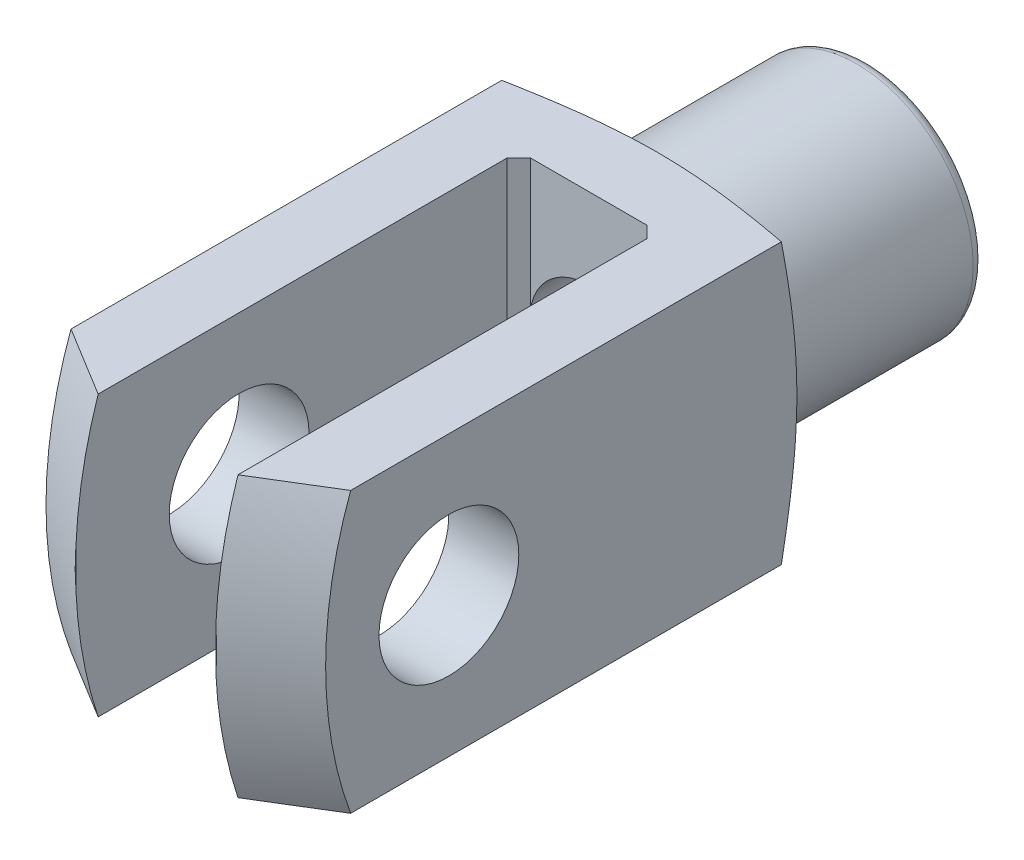
SolidWorks part; units mm, degrees
ref_plane "Front Plane" through (0, 0, 0) normal (0, 0, 1) x (1, 0, 0)
ref_plane "Top Plane" through (0, 0, 0) normal (0, 1, 0) x (1, 0, 0)
ref_plane "Right Plane" through (0, 0, 0) normal (1, 0, 0) x (0, 0, -1)
ref_plane "Plane1" through (0, 0, 0) normal (1, 0, 0) x (0, 0, -1)
sketch "Sketch1" plane through (0, 0, 0) normal (1, 0, 0) x (0, 0, -1)
  line L0 (-14, 0) -> (-14, 24)
  line L1 (-14, 24) -> (26.6506, 24)
  line L2 (26.6506, 24) -> (30, 11.5)
  line L3 (31.5, 10) -> (47, 10)
  line L4 (48, 9) -> (48, 0)
  line L5 (48, 0) -> (-14, 0)
  line L6 (48, 0) -> (-14, 0) construction
  arc A0 (30, 11.5) -> (31.5, 10) centre (31.5, 11.5) ccw
  arc A1 (47, 10) -> (48, 9) centre (47, 9) cw
revolve "Revolve1" add sketch "Sketch1" angle 360 about L6 reverse direction yes
ref_plane "Plane2" through (0, 0, 0) normal (0, 1, 0) x (1, 0, 0)
sketch "Sketch2" plane through (0, 0, 0) normal (0, 1, 0) x (1, 0, 0)
  line L0 (-6, 23) -> (-6, -15)
  line L1 (-6, -15) -> (6, -15)
  line L2 (6, -15) -> (6, 23)
  line L3 (6, 23) -> (5, 24)
  line L4 (5, 24) -> (-5, 24)
  line L5 (-5, 24) -> (-6, 23)
extrude "Cut-Extrude1" cut sketch "Sketch2" against normal blind 25 and the other way blind 25
ref_plane "Plane3" through (0, 0, 0) normal (1, 0, 0) x (0, 0, -1)
sketch "Sketch3" plane through (0, 0, 0) normal (1, 0, 0) x (0, 0, -1)
  line L0 (-39, -36) -> (48, -36)
  line L1 (48, -36) -> (48, -12)
  line L2 (48, -12) -> (-15, -12)
  line L3 (-15, -12) -> (-15, 12)
  line L4 (-15, 12) -> (48, 12)
  line L5 (48, 12) -> (48, 36)
  line L6 (48, 36) -> (-39, 36)
  line L7 (-39, 36) -> (-39, -36)
extrude "Cut-Extrude2" cut sketch "Sketch3" against normal blind 25 and the other way blind 25
ref_plane "Plane4" through (0, 0, 0) normal (0, 1, 0) x (1, 0, 0)
sketch "Sketch4" plane through (0, 0, 0) normal (0, 1, 0) x (1, 0, 0)
  line L0 (-36, -39) -> (36, -39)
  line L1 (36, -39) -> (36, 48)
  line L2 (36, 48) -> (12, 48)
  line L3 (12, 48) -> (12, -15)
  line L4 (12, -15) -> (-12, -15)
  line L5 (-12, -15) -> (-12, 48)
  line L6 (-12, 48) -> (-36, 48)
  line L7 (-36, 48) -> (-36, -39)
extrude "Cut-Extrude3" cut sketch "Sketch4" against normal blind 25 and the other way blind 25
ref_plane "Plane5" through (0, 0, 0) normal (0, 0, 1) x (1, 0, 0)
sketch "Sketch5" plane through (0, 0, 0) normal (0, 0, 1) x (1, 0, 0)
  line L0 (-15.55, 0) -> (-15.55, 6)
  line L1 (-15.55, 6) -> (15.55, 6)
  line L2 (15.55, 6) -> (15.55, 0)
  line L3 (15.55, 0) -> (-15.55, 0)
  line L4 (15.55, 0) -> (-15.55, 0) construction
revolve "Cut-Revolve1" cut sketch "Sketch5" angle 360 about L4 reverse direction yes
ref_plane "Plane6" through (0, 0, 0) normal (1, 0, 0) x (0, 0, -1)
sketch "Sketch6" plane through (0, 0, 0) normal (1, 0, 0) x (0, 0, -1)
  line L0 (22.9, 0) -> (22.9, 5.053)
  line L1 (22.9, 5.053) -> (47.153, 5.053)
  line L2 (47.153, 5.053) -> (48.1, 6)
  line L3 (48.1, 6) -> (48.1, 0)
  line L4 (48.1, 0) -> (22.9, 0)
  line L5 (48.1, 0) -> (22.9, 0) construction
revolve "Cut-Revolve2" cut sketch "Sketch6" angle 360 about L5 reverse direction yes
cosmetic thread "Cosmetic Thread1" parameters "D1"=21.2, "D2"=12
ref_plane "Plane7" through (0, 0, 0) normal (0, 1, 0) x (1, 0, 0)
sketch "Sketch7" plane through (0, 0, 0) normal (0, 1, 0) x (1, 0, 0)
  line L0 (-14, -9.4235) -> (-14, -37.1363)
  line L1 (-14, -37.1363) -> (0, -45.2192)
  line L2 (0, -45.2192) -> (14, -37.1363)
  line L3 (14, -37.1363) -> (14, -9.4235)
  line L4 (14, -9.4235) -> (0, -17.5064)
  line L5 (0, -17.5064) -> (-14, -9.4235)
  line L6 (-14, 24) -> (14, 24) construction
revolve "Cut-Revolve3" cut sketch "Sketch7" angle 90 about L6 other way angle 90 reverse direction yes
